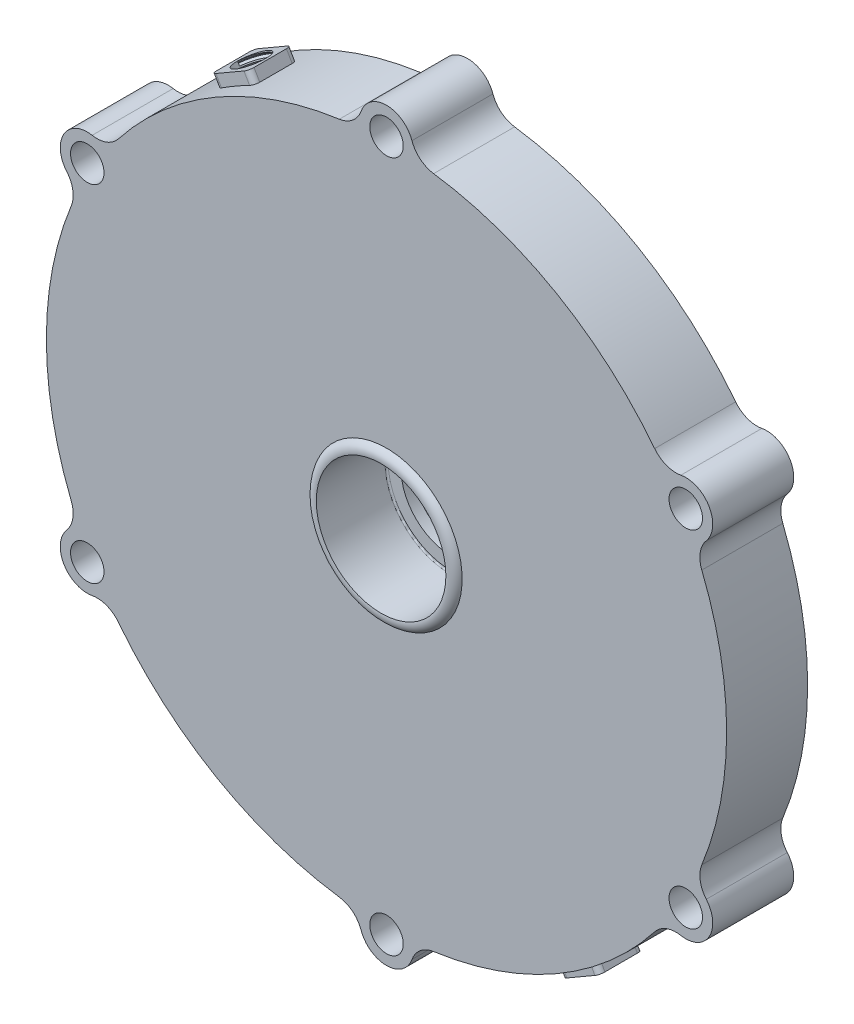
SolidWorks part; units mm, degrees
material "7075-O (SS)"
ref_plane "Front Plane" through (0, 0, 0) normal (0, 0, 1) x (1, 0, 0)
ref_plane "Top Plane" through (0, 0, 0) normal (0, 1, 0) x (1, 0, 0)
ref_plane "Right Plane" through (0, 0, 0) normal (1, 0, 0) x (0, 0, -1)
sketch "Sketch2" plane through (0, 0, 0) normal (1, 0, 0) x (0, 0, -1)
  line L0 (-66.5, 0) -> (66.5, 0) construction
  line L1 (-1.8396, 63) -> (-16.8396, 63)
  line L2 (-16.8396, 63) -> (-16.8396, 13)
  line L3 (-1.8396, 58) -> (-12.8396, 58)
  line L4 (-13.8396, 57) -> (-13.8396, 16)
  line L5 (-1.8396, 63) -> (-1.8396, 58)
  line L6 (-13.8396, 12) -> (-15.8396, 12)
  line L7 (-13.8396, 12) -> (-4.8396, 12)
  line L8 (-4.8396, 12) -> (-4.8396, 9.3148)
  line L9 (-12.8396, 15) -> (-5.9396, 15)
  line L10 (-2.8396, 14) -> (-2.8396, 9.3148)
  line L11 (-4.8396, 9.3148) -> (-2.8396, 9.3148)
  line L12 (-13.8396, 16) -> (-12.8396, 15)
  line L13 (-13.8396, 16) -> (-13.8396, 15) construction
  line L14 (-13.8396, 15) -> (-12.8396, 15) construction
  line L15 (-5.9396, 15) -> (-5.9396, 14.3)
  line L16 (-5.9396, 14.3) -> (-4.6396, 14.3)
  line L17 (-4.6396, 14.3) -> (-4.6396, 15)
  line L18 (-4.6396, 15) -> (-3.8396, 15)
  line L19 (-15.8396, 12) -> (-16.8396, 12)
  line L20 (-16.8396, 12) -> (-16.8396, 13)
  arc A0 (-12.8396, 58) -> (-13.8396, 57) centre (-12.8396, 57) ccw
  arc A1 (-3.8396, 15) -> (-2.8396, 14) centre (-3.8396, 14) cw
  point P4 (0, 0)
  point P22 (-16.8396, 12)
  point P27 (-5.9396, 14.65)
  dimension "D8" = 1
  dimension "D1" = 63
  dimension "D2" = 12
  dimension "D3" = 5
  dimension "D5" = 15
  dimension "D4" = 3
  dimension "D6" = 9
  dimension "D7" = 15
  dimension "D9" = 6.9
  dimension "D10" = 14.3
  dimension "D11" = 1.3
  dimension "D12" = 0.7
revolve "Revolve1" add sketch "Sketch2" angle 360 about L0
sketch "Sketch4" plane through (0, 0, 1.8396) normal (0, 0, -1) x (-1, 0, 0)
  line L0 (0, 0) -> (0, 64) construction
  circle A0 centre (0, 64) radius 5
  circle A2 centre (0, 64) radius 3.1
  circle A8 centre (0, 0) radius 9.3148 construction
  dimension "D1" = 6.2
  dimension "D4" = 10
ref_plane "Plane1" through (31.5, -54.5596, 0) normal (0.5, -0.866, 0) x (0, 0, 1)
sketch "Sketch8" plane through (31.5, -54.5596, 0) normal (0.5, -0.866, 0) x (0, 0, 1)
  line L1 (6.3396, -4) -> (12.3396, -4)
  line L2 (5.3396, -3) -> (5.3396, 3)
  line L3 (6.3396, 4) -> (12.3396, 4)
  line L4 (13.3396, -3) -> (13.3396, 3)
  arc A2 (12.3396, -4) -> (13.3396, -3) centre (12.3396, -3) ccw
  arc A3 (6.3396, -4) -> (5.3396, -3) centre (6.3396, -3) cw
  arc A4 (5.3396, 3) -> (6.3396, 4) centre (6.3396, 3) cw
  arc A5 (12.3396, 4) -> (13.3396, 3) centre (12.3396, 3) cw
  dimension "D3" = 1
extrude "Boss-Extrude2" add sketch "Sketch8" along normal blind 2 and the other way offset from surface (2 mm away) 1
sketch "Sketch9" plane through (32.5, -56.2917, 0) normal (0.5, -0.866, 0) x (0, 0, 1)
  circle A1 centre (9.3396, 0) radius 3
  dimension "D1" = 6
extrude "Cut-Extrude10" cut sketch "Sketch9" against normal blind 11
thread "Thread6" pitch 1 start angle 0, offset 0, length 10, pitch 1, diameter 6
ref_plane "Plane10" through (35.0981, -54.7917, 9.3396) normal (0, 0, 1) x (0.866, 0.5, 0)
sketch "Thread Profile9" plane through (35.0981, -54.7917, 9.3396) normal (0, 0, 1) x (0.866, 0.5, 0)
  line L0 (0, 0) -> (0, 1) construction
  line L1 (0, 0) -> (0.5413, 0.3125)
  line L2 (0.5413, 0.3125) -> (0.5413, 0.4375)
  line L3 (0.5413, 0.4375) -> (0, 0.75)
  line L4 (0.5413, 0.375) -> (0, 0.375) construction
  line L11 (0, 0) -> (0, 0.75)
  point P2 (0, 0)
  dimension "Pitch" = 1
  dimension "Profile_Angle" = 60
  dimension "Profile_Land" = 0.125
  dimension "Profile_Height" = 0.5413
pattern_circular "CirPattern1" count 2 over 360 about axis through (0, 0, 66.5) along (0, 0, 1) of "Boss-Extrude2", "Cut-Extrude10", "Thread6"
sketch "Sketch10" plane through (0, 0, 0) normal (1, 0, 0) x (0, 0, -1)
  line L0 (-1.8396, -63) -> (-1.8396, 63) construction
  line L1 (-1.8396, 60.9) -> (-1.8396, 59)
  line L2 (0, 0) -> (10.6212, 0) construction
  line L4 (-1.8396, 60.9) -> (-2.8396, 60.9)
  line L5 (-1.8396, 60.9) -> (-1.8396, 59)
  line L6 (-1.8396, 59) -> (-2.8396, 59)
  line L7 (-3.1396, 60.6) -> (-3.1396, 59.3)
  arc A1 (-2.8396, 59) -> (-3.1396, 59.3) centre (-2.8396, 59.3) cw
  arc A2 (-2.8396, 60.9) -> (-3.1396, 60.6) centre (-2.8396, 60.6) ccw
  dimension "D2" = 0.3
  dimension "D3" = 1.3
  dimension "D1" = 59
  dimension "D4" = 1.9
revolve "Cut-Revolve1" [suppressed] cut sketch "Sketch10" angle 360 about L2
extrude "Boss-Extrude3" add sketch "Sketch4" against normal up to surface (15 mm away) up to face at (12, 0, 16.8396)
sketch "Sketch11" plane through (0, 0, 1.8396) normal (0, 0, -1) x (-1, 0, 0)
  circle A0 centre (0, 64) radius 3.1 construction
  circle A1 centre (0, 64) radius 3.1
extrude "Cut-Extrude4" cut sketch "Sketch11" against normal up to surface (15 mm away) up to face at (0, 3, 16.8396)
fillet "Fillet2" radius 5 2 edges at (-4.8569, 62.8125, 9.3396) (4.8569, 62.8125, 9.3396)
fillet "Fillet1" [suppressed] radius 1
pattern_circular "CirPattern2" count 6 over 360 about axis through (0, 0, 0) along (0, 0, 1) of "Boss-Extrude3", "Cut-Extrude4", "Fillet2"
sketch "Sketch12" plane through (0, 0, 0) normal (0, 1, 0) x (1, 0, 0)
  line L1 (12, -16.8396) -> (14.0082, -16.8396)
  line L2 (12, -16.8396) -> (0, -16.8396)
  line L3 (0, -16.8396) -> (0, -17.8396)
  line L4 (0, -17.8396) -> (12, -17.8396)
  arc A0 (14.0082, -16.8396) -> (12, -17.8396) centre (12.3834, -16.0932) cw
  dimension "D1" = 1
revolve "Revolve2" add sketch "Sketch12" angle 360 about L3
sketch "Sketch13" plane through (0, 0, 17.8396) normal (0, 0, 1) x (1, 0, 0)
  circle A0 centre (0, 0) radius 12
extrude "Cut-Extrude5" cut sketch "Sketch13" against normal blind 1
fillet "Fillet3" radius 0.3 1 edges at (12, 0, 4.8396)
